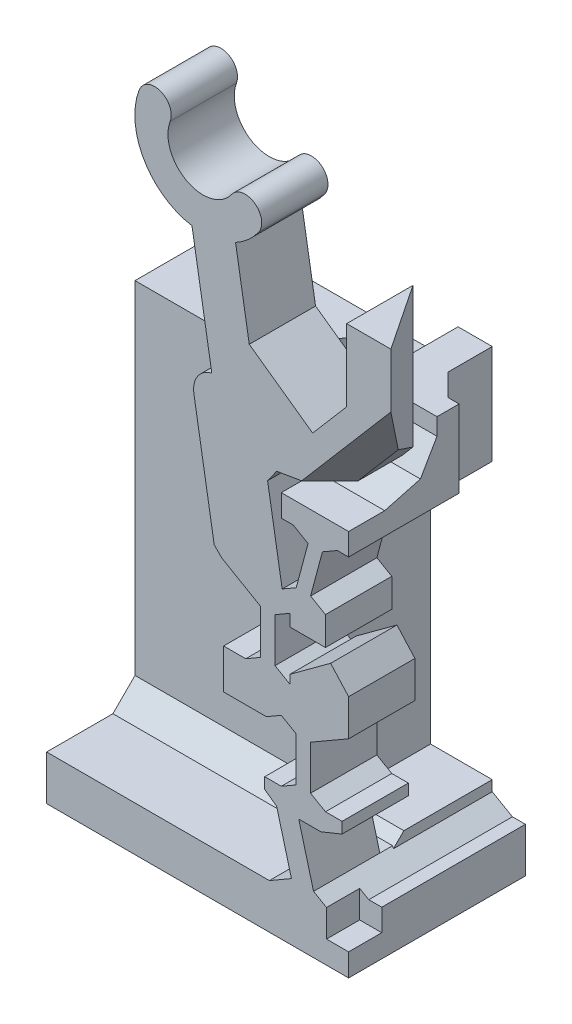
SolidWorks part; units mm, degrees
material "Nylon 6/12"
ref_plane "Front Plane" through (0, 0, 0) normal (0, 0, 1) x (1, 0, 0)
ref_plane "Top Plane" through (0, 0, 0) normal (0, 1, 0) x (1, 0, 0)
ref_plane "Right Plane" through (0, 0, 0) normal (1, 0, 0) x (0, 0, -1)
sketch "Sketch-SkeletonConfigUp" plane through (0, 0, 0) normal (0, 0, 1) x (1, 0, 0)
  line L0 (0, 0) -> (0, -50000) construction
  line L1 (0, 0) -> (4.5811, 6.2164) construction
  line L2 (9.8143, 13.3177) -> (4.5811, 13.945) construction
  line L3 (4.5811, 13.945) -> (2.9713, 10.4094) construction
  line L4 (2.9713, 10.4094) -> (4.5811, 6.2164) construction
  line L5 (4.5811, 13.945) -> (6.2429, 19.1409) construction
  line L6 (2.9713, 10.4094) -> (0.0405, 27.8193) construction
  line L7 (4.5811, 6.2164) -> (9.8143, 13.3177) construction
  line L8 (-587.3593, -797.0242) -> (9.8143, 13.3177) construction
  dimension "D2" = 7.7221
  dimension "D3" = 8.8212
  dimension "D4" = 5.2707
  dimension "D5" = 119.553
  dimension "D6" = 3.8848
  dimension "D7" = 5.4552
  dimension "D8" = 17.6549
  dimension "D9" = 4.4914
  dimension "D10" = 6.745
  dimension "D11" = 145.964
  dimension "D12" = 143.612
sketch "Sketch-SkeletonConfigDown" plane through (0, 0, 0) normal (0, 0, 1) x (1, 0, 0)
  line L0 (0, 0) -> (0, -50000) construction
  line L1 (0, 0) -> (4.5811, 6.2164) construction
  line L2 (9.8143, 13.3177) -> (4.5811, 13.945) construction
  line L3 (4.5811, 13.945) -> (6.1909, 10.4094) construction
  line L4 (6.1909, 10.4094) -> (4.5811, 6.2164) construction
  line L5 (4.5811, 13.945) -> (1.753, 18.6098) construction
  line L6 (6.1909, 10.4094) -> (-8.8652, 19.6294) construction
  line L7 (4.5811, 6.2164) -> (9.8143, 13.3177) construction
  line L8 (-589.9357, -800.5203) -> (9.8143, 13.3177) construction
  dimension "D2" = 7.7221
  dimension "D3" = 8.8212
  dimension "D4" = 5.2707
  dimension "D5" = 119.553
  dimension "D6" = 3.8848
  dimension "D7" = 5.4552
  dimension "D8" = 17.6549
  dimension "D9" = 4.4914
  dimension "D10" = 6.745
  dimension "D11" = 145.964
  dimension "D1" = 143.612
ref_plane "Plane-Cam Base" through (9.128, 0, 0) normal (1, 0, 0) x (0, 0, -1)
ref_plane "Plane-Down-to-Up Derailleur Clearance" through (6.628, 0, 0) normal (1, 0, 0) x (0, 0, -1)
ref_plane "Plane-Cam Cavity Roof" through (5.128, 0, 0) normal (1, 0, 0) x (0, 0, -1)
sketch "Sketch-SwitchBossUp" plane through (0, 0, 0) normal (0, 0, 1) x (1, 0, 0)
  line L0 (3.5811, 11.4759) -> (3.5811, 12.945) construction
  line L2 (6.5405, 21.1774) -> (6.5405, 24.4384)
  line L3 (6.5405, 24.4384) -> (8.5405, 24.4384)
  line L4 (8.5405, 24.4384) -> (8.5405, 20.4384)
  line L5 (5.5811, 12.5552) -> (5.5811, 11.263)
  line L7 (1.5115, 25.1048) -> (2.5464, 18.9575)
  line L8 (-0.4607, 24.7728) -> (0.4359, 19.4465)
  line L9 (2.9713, 10.4094) -> (0.0405, 27.8193) construction
  line L11 (-0.0396, 22.2712) -> (1.9326, 22.6032) construction
  line L15 (6.628, -55) -> (6.628, 55) construction
  line L16 (2.9713, 10.4094) -> (4.5811, 6.2164) construction
  line L17 (3.5811, 12.945) -> (3.5811, 14.945) construction
  line L18 (5.5811, 12.945) -> (5.5811, 14.945) construction
  line L19 (4.2561, 13.945) -> (4.9061, 13.945) construction
  line L20 (3.5811, 14.945) -> (5.5811, 14.945) construction
  line L21 (3.5811, 12.945) -> (5.5811, 12.945) construction
  line L22 (4.5811, 12.945) -> (4.5811, 14.945) construction
  line L23 (4.5811, 6.2164) -> (8.5405, 7.1023) construction
  line L24 (1.9713, 9.4094) -> (1.9713, 11.4094) construction
  line L25 (3.9713, 9.4094) -> (3.9713, 11.4094) construction
  line L26 (3.9713, 9.4094) -> (1.9713, 9.4094) construction
  line L27 (1.9713, 11.4094) -> (3.9713, 11.4094) construction
  line L28 (3.5811, 7.2164) -> (5.5811, 7.2164) construction
  line L29 (3.5811, 7.2164) -> (3.5811, 5.2164) construction
  line L30 (5.5811, 7.2164) -> (5.5811, 5.2164) construction
  line L31 (3.5811, 5.2164) -> (5.5811, 5.2164) construction
  line L32 (4.9061, 6.2164) -> (4.2561, 6.2164) construction
  line L40 (3.2963, 10.4094) -> (2.6463, 10.4094) construction
  line L43 (2.874, 4.5093) -> (0.7934, 4.5093) construction
  line L51 (4.9929, 19.3693) -> (2.5464, 18.9575)
  line L66 (0.0405, 27.8193) -> (0.0405, 50027.8193) construction
  line L74 (0.5455, 12.7717) -> (-0.3728, 18.2264)
  line L75 (0.3841, 13.7302) -> (2.3564, 14.0622) construction
  line L76 (5.5811, 11.263) -> (5.5811, 12.5552) construction
  line L77 (5.5811, 7.6061) -> (6.628, 8.2105)
  line L80 (5.8152, 10.763) -> (6.628, 9.8603)
  line L81 (8.5405, 1033.6218) -> (8.5405, 20.4384) construction
  line L82 (2.5464, 18.9575) -> (3.5585, 12.945) construction
  line L83 (3.6203, 12.5779) -> (2.8784, 16.9852)
  line L84 (2.8784, 16.9852) -> (6.0405, 17.5175)
  line L85 (6.9307, 9.5241) -> (8.5405, 7.7363) construction
  line L88 (3.5811, 16.3347) -> (6.8573, 16.3347)
  line L92 (3.7762, 8.3129) -> (6.9307, 9.5241) construction
  line L93 (6.3311, 4.3267) -> (5.3706, 3.937)
  line L95 (2.5464, 18.9575) -> (2.8784, 16.9852) construction
  line L96 (2.7124, 17.9713) -> (8.5405, 18.9524) construction
  line L97 (2.7124, 17.9713) -> (1.7262, 17.8053) construction
  line L98 (1.9713, 9.0197) -> (0.9713, 9.0197)
  line L99 (0.9713, 9.0197) -> (0.9713, 7.2164)
  line L100 (0.9713, 7.2164) -> (2.9061, 7.2164)
  line L101 (4.5811, 6.2164) -> (6.9307, 9.5241) construction
  line L103 (0.0405, 27.8193) -> (1.9448, 26.4638) construction
  line L104 (6.9307, 9.5241) -> (8.5405, 7.7363) construction
  line L106 (13.4416, 14.945) -> (5.5811, 14.945) construction
  line L107 (1.9713, 9.4094) -> (1.9713, 9.0197) construction
  line L109 (0.0405, 27.8193) -> (-2.1498, 28.6358) construction
  line L110 (8.5405, 20.4384) -> (6.0405, 17.5175)
  line L111 (6.628, 9.8603) -> (6.628, 8.2105)
  line L112 (6.628, 9.8603) -> (6.9307, 9.5241) construction
  line L113 (2.8311, 4.8267) -> (2.8311, 4.3267)
  line L114 (7.3693, 7.7363) -> (7.3563, 7.7363) construction
  line L115 (6.8573, 16.3347) -> (13.4416, 16.3347)
  line L116 (13.4416, 16.3347) -> (13.4416, -1.1653)
  line L117 (13.4416, -1.1653) -> (5.0405, -1.1653)
  line L119 (10.4375, 14.0252) -> (10.4375, 2.1692)
  line L121 (5.0405, -1.1653) -> (5.0405, 1.437) construction
  line L122 (8.237, 12.8031) -> (10.8393, 12.8031) construction
  line L123 (10.8393, 12.8031) -> (13.4416, 12.8031) construction
  line L124 (10.4375, 2.1692) -> (9.128, 0.8597)
  line L125 (8.5405, 7.5847) -> (13.4416, 7.5847) construction
  line L127 (5.5811, 15.3347) -> (5.5811, 14.945) construction
  line L130 (6.0405, 0.8597) -> (9.128, 0.8597)
  line L132 (2.8311, 4.3267) -> (3.3706, 3.937)
  line L133 (2.9713, 10.4094) -> (6.1909, 10.4094) construction
  line L134 (4.5811, 10.4094) -> (4.5811, 13.945) construction
  line L135 (4.5811, 10.4094) -> (4.5811, 6.2164) construction
  line L136 (0.8973, 12.4192) -> (0.5455, 12.7717)
  line L137 (3.9713, 9.4094) -> (5.5811, 7.2164) construction
  line L139 (5.8152, 10.763) -> (3.9713, 9.4094)
  line L141 (4.0405, 1.437) -> (3.0405, 0.8597)
  line L142 (3.0405, 0.8597) -> (3.0405, -1.1653)
  line L143 (8.5405, 20.4384) -> (8.5405, 18.9524) construction
  line L145 (8.5405, 17.9384) -> (8.5405, -49992.0368) construction
  line L147 (5.5811, 11.263) -> (5.5811, 12.5552) construction
  line L149 (6.3311, 4.8267) -> (6.3311, 4.3267)
  line L150 (3.0405, -1.1653) -> (5.0405, -1.1653)
  line L151 (3.3706, 3.937) -> (5.3706, 3.937) construction
  line L152 (4.792, 14.945) -> (4.2561, 12.945)
  line L153 (5.442, 14.945) -> (4.9061, 12.945)
  line L157 (3.5811, 16.3347) -> (3.5811, 15.3347)
  line L158 (6.117, 15.3347) -> (9.128, 15.3347)
  line L162 (3.2963, 11.4094) -> (3.2963, 9.4094)
  line L164 (2.6463, 11.4094) -> (2.6463, 9.4094)
  line L169 (4.2561, 7.2164) -> (4.2561, 5.2164)
  line L170 (4.9061, 5.2164) -> (4.9061, 7.2164)
  line L175 (4.2561, 7.2164) -> (3.5811, 7.6061)
  line L176 (4.9061, 7.2164) -> (5.5811, 7.6061)
  line L177 (5.5811, 7.2164) -> (5.5811, 7.6061) construction
  line L179 (4.2561, 5.2164) -> (3.5811, 4.8267)
  line L180 (3.5811, 5.2164) -> (3.5811, 4.8267) construction
  line L181 (3.5811, 4.8267) -> (2.8311, 4.8267)
  line L183 (4.9061, 5.2164) -> (5.5811, 4.8267)
  line L184 (5.5811, 5.2164) -> (5.5811, 4.8267) construction
  line L186 (9.128, -55) -> (9.128, 55) construction
  line L187 (2.6463, 9.4094) -> (1.9713, 9.0197)
  line L188 (3.2963, 9.4094) -> (3.9713, 9.0197)
  line L189 (3.2963, 11.4094) -> (3.9713, 11.7991)
  line L190 (2.6463, 11.4094) -> (0.8973, 12.4192)
  line L191 (3.9713, 11.4094) -> (3.9713, 11.7991) construction
  line L192 (3.9713, 11.7991) -> (3.9713, 11.263)
  line L193 (4.9061, 12.945) -> (5.5811, 12.5552)
  line L194 (4.2561, 12.945) -> (3.6203, 12.5779)
  line L195 (3.9713, 11.263) -> (5.5811, 11.263)
  line L196 (3.9713, 9.4094) -> (3.9713, 9.0197)
  line L197 (3.5811, 7.2164) -> (3.5811, 7.6061) construction
  line L199 (3.5811, 7.6061) -> (2.9061, 7.2164)
  line L200 (5.5811, 4.8267) -> (6.3311, 4.8267)
  line L201 (2.8311, 4.3267) -> (2.8311, 3.937) construction
  line L202 (2.8311, 3.937) -> (3.3706, 3.937) construction
  line L203 (10.4375, 14.0252) -> (9.128, 15.3347)
  line L204 (5.0405, 1.437) -> (3.0405, 1.437) construction
  line L205 (3.0405, 1.437) -> (3.0405, 0.8597) construction
  line L206 (5.0405, 1.437) -> (6.0405, 0.8597)
  line L207 (8.5405, 18.9524) -> (8.5405, 17.9384) construction
  line L208 (6.0405, 17.5175) -> (8.5405, 17.9384) construction
  line L209 (8.5405, 20.4384) -> (8.5405, 17.9384) construction
  line L210 (6.5405, 21.1774) -> (4.9929, 19.3693)
  line L211 (5.0405, 1.437) -> (4.3706, 3.937)
  line L212 (4.0405, 1.437) -> (3.3706, 3.937)
  line L213 (5.3706, 3.937) -> (4.3706, 3.937)
  line L214 (4.792, 14.945) -> (4.1169, 15.3347)
  line L215 (4.1169, 15.3347) -> (3.5811, 15.3347)
  line L216 (5.442, 14.945) -> (6.117, 15.3347)
  line L217 (5.5811, 12.945) -> (5.5811, 12.5552) construction
  line L218 (5.442, 14.945) -> (5.442, 15.3347) construction
  line L219 (6.117, 15.3347) -> (4.1169, 15.3347) construction
  arc A0 (1.5115, 25.1048) -> (2.5558, 26.0289) centre (0.0405, 27.8193) ccw
  arc A1 (-0.4607, 24.7728) -> (-2.8525, 28.8978) centre (0.0405, 27.8193) cw
  arc A2 (-2.8525, 28.8978) -> (-1.447, 28.3738) centre (-2.1498, 28.6358) cw
  arc A3 (2.5558, 26.0289) -> (1.3338, 26.8987) centre (1.9448, 26.4638) ccw
  arc A4 (-1.447, 28.3738) -> (1.3338, 26.8987) centre (0.0405, 27.8193) ccw
  arc A5 (3.5811, 12.945) -> (3.5811, 14.945) centre (3.1778, 13.945) ccw construction
  arc A6 (5.5811, 12.945) -> (5.5811, 14.945) centre (5.9843, 13.945) cw construction
  arc A7 (2.5293, 9.921) -> (1.9713, 11.4094) centre (1.568, 10.4094) ccw construction
  arc A8 (3.9713, 11.4094) -> (3.9713, 9.4094) centre (4.3745, 10.4094) ccw construction
  arc A9 (3.5811, 7.2164) -> (3.5811, 5.2164) centre (3.1779, 6.2164) cw construction
  arc A10 (5.5811, 7.2164) -> (5.5811, 5.2164) centre (5.9844, 6.2164) ccw construction
  arc A19 (-0.3728, 18.2264) -> (0.4359, 19.4465) centre (0.6836, 18.4042) cw
  circle A28 centre (0.0405, 27.8193) radius 2.3375 construction
  arc A29 (1.9713, 9.4094) -> (2.5293, 9.921) centre (1.568, 10.4094) ccw construction
  point P53 (4.5811, 13.945)
  point P63 (2.9713, 10.4094)
  point P93 (0.9465, 22.4372)
  dimension "D23" = 1.5875
  dimension "D24" = 0.75
  dimension "D2" = 2
  dimension "D5" = 2
  dimension "D6" = 0.65
  dimension "D8" = 42
  dimension "D7" = 2
  dimension "D11" = 8.5
  dimension "D14" = 7.5
  dimension "D4" = 3
  dimension "D16" = 42
  dimension "D27" = 120
  dimension "D28" = 120
  dimension "D29" = 120
  dimension "D30" = 120
  dimension "D31" = 120
  dimension "D32" = 120
  dimension "D33" = 120
  dimension "D34" = 120
  dimension "D17" = 0.5
  dimension "D20" = 3.5
  dimension "D21" = 1
  dimension "D18" = 45
  dimension "D9" = 17.5
  dimension "D22" = 1
  dimension "D15" = 45
  dimension "D38" = 2
  dimension "D39" = 0.5
  dimension "D40" = 60
  dimension "D41" = 1
  dimension "D42" = 45
  dimension "D43" = 120
  dimension "D44" = 2
  dimension "D45" = 2.5
  dimension "D46" = 2.5
  dimension "D47" = 4
  dimension "D48" = 2
  dimension "D10" = 15
  dimension "D12" = 2.5
  dimension "D13" = 1
  dimension "D19" = 1
  dimension "D25" = 15
  dimension "D26" = 120
  dimension "D35" = 120
extrude "Boss-Switch Body" add sketch "Sketch-SwitchBossUp" along normal blind 3
sketch "Sketch1" plane through (0, 0, 0) normal (0, 0, -1) x (-1, 0, 0)
  line L1 (-7.5811, -1.1653) -> (0.4122, -1.1653)
  line L2 (-7.5811, -1.1653) -> (-7.5811, 0.8597)
  line L4 (0.4122, -1.1653) -> (0.4122, 0.8597)
  line L5 (-3.5811, 18.8347) -> (-7.5811, 18.8347)
  line L10 (-7.5811, 18.8347) -> (-7.5811, 15.3347)
  line L11 (-4.0405, 1.437) -> (-5.0405, 1.437)
  line L12 (-7.5811, 15.3347) -> (-3.5811, 15.3347)
  line L13 (-4.0405, 1.437) -> (-3.0405, 0.8597)
  line L14 (-3.5811, 15.3347) -> (-3.5811, 18.8347)
  line L20 (-4.3706, 3.937) -> (-5.0405, 1.437) construction
  line L22 (-3.0405, -1.1653) -> (-13.4416, -1.1653) construction
  line L23 (-3.0405, 0.8597) -> (0.4122, 0.8597)
  line L24 (-5.0405, 1.437) -> (-6.0405, 0.8597)
  line L25 (-6.0405, 0.8597) -> (-7.5811, 0.8597)
  line L27 (-3.5811, 16.3347) -> (-3.5811, 15.3347) construction
  dimension "D1" = 3.5
  dimension "D4" = 4
extrude "Boss-Flange Width" add sketch "Sketch1" along normal blind 5
ref_plane "Plane-Sta2Sit Groove" through (0.0405, 0, 0) normal (1, 0, 0) x (0, 0, -1)
ref_plane "Plane-Cam Outer Surface" through (-12.0395, 0, 0) normal (1, 0, 0) x (0, 0, -1)
ref_plane "Plane-FlangeTop" through (-7.0395, 0, 0) normal (1, 0, 0) x (0, 0, -1)
sketch "Sketch2" plane through (-7.0395, 0, 0) normal (1, 0, 0) x (0, 0, -1)
  line L0 (5, 15.3347) -> (-3, 15.3347) construction
  line L1 (5, 17.3347) -> (1, 17.3347)
  line L2 (5, 17.3347) -> (5, 15.3347)
  line L3 (5, 15.3347) -> (1, 15.3347)
  line L4 (1, 17.3347) -> (1, 15.3347)
  line L10 (-3, -1.1653) -> (-3, 16.3347) construction
  line L11 (5, 0.8597) -> (-3, 0.8597)
  line L12 (5, 0.8597) -> (5, -1.1653)
  line L13 (5, -1.1653) -> (-3, -1.1653)
  line L14 (-3, 0.8597) -> (-3, -1.1653)
  line L15 (0, 10.4094) -> (0, 27.8193) construction
  line L17 (5, 0.8597) -> (5, -1.1653) construction
  line L18 (-3, 0.8597) -> (0, 0.8597) construction
  dimension "D1" = 1
  dimension "D2" = 2
extrude "Boss-Flange Height" add sketch "Sketch2" along normal up to surface (11.6675 mm away)
sketch "Sketch10" plane through (0, 15.3347, 0) normal (0, 1, 0) x (1, 0, 0)
  line L0 (9.128, -55) -> (9.128, 55) construction
  line L1 (7.5811, 5) -> (5.128, 5)
  line L2 (7.5811, 5) -> (7.5811, 2)
  line L3 (7.5811, 2) -> (5.128, 2)
  line L5 (4.628, 7) -> (4.628, 1) construction
  line L6 (3.5811, 1) -> (-7.0395, 1) construction
  line L8 (5.128, 5) -> (5.128, 2)
  dimension "D1" = 1
  dimension "D2" = 0.5
  dimension "D3" = 4.5
extrude "Cut-Up-To-Down Derailleur Clearance" cut sketch "Sketch10" along normal up to next
sketch "Sketch17" plane through (0, 15.3347, 0) normal (0, -1, 0) x (1, 0, 0)
  line L0 (5.128, -5) -> (-7.0395, -5)
  line L1 (5.128, -5) -> (-7.0395, -5) construction
  line L2 (-7.0395, -5) -> (-7.0395, -1)
  line L3 (-7.0395, -1) -> (5.128, -1)
  line L4 (5.128, -1) -> (5.128, -5)
  line L5 (-7.0395, -1) -> (-7.0395, -5) construction
extrude "Boss-Flange Support" add sketch "Sketch17" along normal up to surface (14.475 mm away) up to face at (-1.9995, 0.8597, -1)
sketch "Sketch-HolePositions" plane through (0, -1.1653, 0) normal (0, -1, 0) x (1, 0, 0)
  line L0 (-7.0395, -3) -> (7.5811, -3) construction
  line L1 (7.5811, -5) -> (-7.0395, -5) construction
  line L2 (7.5811, -5) -> (7.5811, 0) construction
  line L4 (-7.0395, -22.2167) -> (-7.0395, 22.2167) construction
  line L5 (3.5811, -1) -> (3.5811, -5) construction
  point P6 (-4.0395, -3)
  point P7 (0.5811, -3)
  dimension "D1" = 3
  dimension "D2" = 3
  dimension "D3" = 2
sketch "Sketch6" plane through (0, -1.1653, 0) normal (0, -1, 0) x (-1, 0, 0)
  point P0 (4.0395, 3)
  point P3 (-0.5811, 3)
hole_wizard "Tap Drill for M2x0.4 Tap1" positions "Sketch6" profile "Sketch5" hole size "M2x0.4" standard "ANSI Metric" end condition through all
sketch "Sketch5" plane through (-4.0395, -1.1653, -3) normal (1, 0, 0) x (0, 0, -1)
  line L0 (0, 0) -> (0, 30.5511)
  line L1 (0, 30.5511) -> (0.8, 30.5511)
  line L2 (0.8, 30.5511) -> (0.8, 0)
  line L5 (0.8, 0) -> (0, 0)
  line L11 (0, -6.35) -> (0, 107.95) construction
  dimension "Thru Hole Dia." = 1.6
  dimension "Thru Hole Depth" = 30.5511
sketch "Sketch9" plane through (0, -1.1653, 0) normal (0, -1, 0) x (1, 0, 0)
  point P0 (-4.0395, -3)
  point P3 (0.5811, -3)
hole_wizard "M2 Clearance Hole2" positions "Sketch9" profile "Sketch8" hole size "M2" standard "ANSI Metric"
sketch "Sketch8" plane through (-4.0395, -1.1653, -3) normal (1, 0, 0) x (0, 0, -1)
  line L0 (0, 0) -> (0, 15.721)
  line L1 (0, 15.721) -> (1.2, 15)
  line L2 (1.2, 15) -> (1.2, 0)
  line L5 (1.2, 0) -> (0, 0)
  line L10 (0, 15.721) -> (-1.2, 15) construction
  line L11 (0, -6.35) -> (0, 107.95) construction
  dimension "Hole Dia." = 2.4
  dimension "Hole Depth" = 15
  dimension "Drill Angle" = 118
sketch "Sketch-Measurements for Derailleur Ramps" plane through (0, 0, 0) normal (0, 0, 1) x (1, 0, 0)
  line L0 (2.8784, 16.9852) -> (2.5464, 18.9575)
  line L1 (2.7124, 17.9713) -> (1.7262, 17.8053)
  line L2 (2.9713, 10.4094) -> (0.0405, 27.8193) construction
  line L3 (1.7262, 17.8053) -> (-1.8937, 15.3603)
  line L4 (6.1909, 10.4094) -> (-8.8652, 19.6294) construction
  line L5 (1.7262, 17.8053) -> (2.6012, 12.6077)
  line L6 (2.6012, 12.6077) -> (-1.8937, 15.3603)
  line L7 (-0.0837, 16.5828) -> (-0.0837, 17.8053)
  line L8 (-0.0837, 17.8053) -> (1.7262, 17.8053)
  line L9 (6.1909, 10.4094) -> (2.9713, 10.4094)
  line L10 (5.386, 8.3129) -> (3.7762, 8.3129)
  line L12 (6.1909, 10.4094) -> (4.5811, 6.2164) construction
  line L13 (4.5811, 8.3129) -> (4.5811, 8.7912)
  line L14 (4.5811, 6.2164) -> (5.386, 8.3129)
  line L15 (2.9713, 10.4094) -> (4.5811, 6.2164) construction
  line L16 (3.7762, 8.3129) -> (4.5811, 6.2164)
  line L17 (5.386, 8.3129) -> (5.386, 8.7912)
  dimension "D1" = 1.81
  dimension "D2" = 0.8049
sketch "Sketch12" plane through (0, 24.4384, 0) normal (0, 1, 0) x (1, 0, 0)
  line L0 (6.5405, 0) -> (8.5405, -3)
  line L1 (8.5405, -3) -> (8.5405, 0)
  line L2 (8.5405, 0) -> (6.5405, 0)
extrude "Cut-Up-to-Down Cantilever Slope" cut sketch "Sketch12" against normal up to next
ref_plane "Plane1" through (0, 7.1023, 0) normal (0, 1, 0) x (1, 0, 0)
sketch "Sketch-Derailleur Location" plane through (0, 7.1023, 0) normal (0, 1, 0) x (1, 0, 0)
  line L0 (8.5405, 0) -> (8.5405, -3)
  line L1 (4.0405, -3) -> (3.0405, -3) construction
  line L2 (-119237.4187, 0) -> (9.8143, 0) construction
  point P0 (8.5405, 0)
  point P8 (8.5405, -1.5)
ref_plane "Plane-Cantilever Cut" [suppressed] through (7.0848, 8.5204, -1.9058) normal (-0.6301, -0.7578, 0.1695) x (-0.7765, 0.6151, -0.1368)
sketch "Sketch14" [suppressed] plane through (7.0848, 8.5204, -1.9058) normal (-0.6301, -0.7578, 0.1695) x (-0.7765, 0.6151, -0.1368)
  line L0 (2.3023, -1.6911) -> (-0.3551, -1.6911)
  line L2 (2.3023, -4.3362) -> (2.3023, -1.6911)
  line L3 (-0.3551, -1.6911) -> (-0.3551, -4.4608)
  line L5 (-0.3551, -4.4608) -> (1.0087, -5.0843)
  line L6 (1.0087, -5.0843) -> (2.3023, -4.3362)
extrude "Cut-Down-to-Up Cantilever Slope" [suppressed] cut sketch "Sketch14" against normal up to next
sketch "Sketch16" plane through (0, 0, 0) normal (0, 0, -1) x (-1, 0, 0)
  line L0 (-7.5811, 18.8347) -> (-13.4416, 18.8347)
  line L1 (-13.4416, 18.8347) -> (-13.4416, -1.1653)
  line L2 (-13.4416, -1.1653) -> (-6.628, -1.1653)
  line L3 (-13.4416, -1.1653) -> (-5.0405, -1.1653) construction
  line L4 (-6.628, -1.1653) -> (-6.628, 5.2038)
  line L5 (-6.628, 5.2038) -> (-8.0037, 5.2038)
  line L6 (-8.0037, 5.2038) -> (-8.0037, 12.0484)
  line L7 (-8.0037, 12.0484) -> (-6.628, 12.0484)
  line L8 (-6.628, 12.0484) -> (-6.628, 17.9477)
  line L9 (-6.628, 55) -> (-6.628, -55) construction
  line L10 (-3.5811, 18.8347) -> (-6.5405, 18.8347) construction
  line L11 (-7.5811, 18.8347) -> (-6.628, 17.9477)
extrude "Cut-Down-to-Up Derailleur Clearance" cut sketch "Sketch16" against normal through all and the other way through all
ref_plane "Plane-Symmetry Plane" through (0, 0, 1.5) normal (0, 0, 1) x (1, 0, 0)
sketch "Sketch-Cable Center Point" plane through (0, 0, 1.5) normal (0, 0, 1) x (1, 0, 0)
  line L0 (0.0405, 27.8193) -> (0.1722, 27.0366)
  line L1 (2.9713, 10.4094) -> (0.0405, 27.8193) construction
  point P0 (0.0405, 27.8193)
  dimension "D1" = 0.7937
chamfer "Chamfer-Flange Support" distance 1.5 angle 45 1 edges at (3.5811, 17.3347, -3)
chamfer "Chamfer-Flange Support 2" distance 1 angle 45 2 edges at (5.128, 17.0847, -2) (5.128, 15.3347, -1.5)
chamfer "Chamfer-Flange Support 3" distance 1 angle 45 1 edges at (-1.9995, 0.8597, -1)
sketch "Sketch18" plane through (6.628, 0, 0) normal (1, 0, 0) x (0, 0, -1)
  line L1 (-3, -0.1403) -> (-1.5, -0.1403)
  line L2 (-3, -0.1403) -> (-3, 1.437)
  line L3 (-3, 1.437) -> (-1.5, 1.437)
  line L4 (-1.5, -0.1403) -> (-1.5, 1.437)
  line L5 (0.5774, 1.437) -> (0, 1.437) construction
  line L6 (-3, -1.1653) -> (-3, 0.8597) construction
  line L7 (-3, 0.8597) -> (5, 0.8597) construction
  dimension "D1" = 1.5
  dimension "D2" = 1
extrude "Cut-Down-to-Up Derailleur Clearance 2" cut sketch "Sketch18" against normal blind 1
sketch "Sketch19" plane through (0, 0, 0) normal (0, 0, 1) x (1, 0, 0)
  line L7 (3.5811, 18.8983) -> (6.628, 18.8983)
  line L8 (6.628, 18.8983) -> (6.628, 16.3347)
  line L9 (6.628, 16.3347) -> (3.5811, 16.3347)
  line L10 (3.5811, 16.3347) -> (3.5811, 18.8983)
  line L11 (6.628, 16.3347) -> (6.628, 17.9477) construction
extrude "Cut-Up-to-Down Cantilever Clearance" cut sketch "Sketch19" against normal up to surface (1 mm away) up to face at (1.4435, 12.7784, -1)
chamfer "Chamfer1" distance 1 angle 60 1 edges at (5.1045, 16.3347, -1) first distance on face at (5.1045, 16.3347, 1)
chamfer "Chamfer3" distance 0.75 angle 60 1 edges at (3.5811, 16.7007, -1) first distance on face at (3.5811, 16.2811, 0.8)
chamfer "Chamfer4" distance 0.5 angle 60 1 edges at (4.205, 15.3347, -1) first distance on face at (5.0385, 15.3347, 0.5227)
chamfer "Chamfer5" distance 0.5 angle 45 1 edges at (2.8784, 16.9852, 1.5)
chamfer "Chamfer6" distance 2.5 angle 45 1 edges at (2.5464, 18.9575, 1.5)
chamfer "Chamfer7" distance 1 angle 45 1 edges at (7.2905, 18.978, 3)
sketch "Sketch22" plane through (0, 0, 0) normal (0, 0, 1) x (1, 0, 0)
  line L0 (6.628, 17.9477) -> (7.5811, 18.8347) construction
  line L1 (6.628, 18.8347) -> (7.5811, 18.8347) construction
  line L2 (6.628, 17.9477) -> (6.628, 18.8347) construction
  line L3 (6.628, 17.9477) -> (7.5811, 18.8347)
  line L4 (6.628, 18.8347) -> (7.5811, 18.8347)
  line L5 (6.628, 17.9477) -> (6.628, 18.8347)
extrude "Cut-Extrude3" cut sketch "Sketch22" against normal up to next
chamfer "Chamfer8" distance 0.5 angle 45 1 edges at (5.1045, 16.3347, 0) first distance on face at (4.2965, 17.2286, -0.5161)
sketch "Sketch23" plane through (0, 0, -1) normal (0, 0, 1) x (1, 0, 0)
  line L0 (5.128, 1.8597) -> (2.3369, 1.8597)
  line L1 (-7.0395, 1.8597) -> (5.128, 1.8597) construction
  line L2 (2.3369, 1.8597) -> (2.3369, 14.3347)
  line L3 (2.3369, 14.3347) -> (5.128, 14.3347)
  line L4 (5.128, 14.3347) -> (5.128, 1.8597)
extrude "Cut-Extrude4" cut sketch "Sketch23" against normal through all
equation "\"axle-diameter\"=2"
equation "\"switch-thickness\"=12"
equation "\"base-width\"=4.0"
equation "\"axle-bushing-radius\"=3"
equation "\"clearance\"= 0.25"
equation "\"arm-width\"=1.5"
equation "\"min-diameter\"=70"
equation "\"alpha\"=143.6120"
equation "\"gamma\"=119.5526"
equation "\"delta\"=145.9637"
equation "\"epsilon\"=6.7452"
equation "\"l_AB\"=8.8212"
equation "\"l_AC\"=4.4914"
equation "\"l_BD\"=5.2707"
equation "\"l_CD\"=3.8848"
equation "\"l_CE\"=17.6549"
equation "\"l_DF\"=5.4552"
equation "\"l_OA\"=7.7221"
equation "\"D2@Sketch-SkeletonConfigUp\" = \"l_OA\""
equation "\"D3@Sketch-SkeletonConfigUp\" = \"l_AB\""
equation "\"D4@Sketch-SkeletonConfigUp\" = \"l_BD\""
equation "\"D5@Sketch-SkeletonConfigUp\" = \"gamma\""
equation "\"D6@Sketch-SkeletonConfigUp\" = \"l_CD\""
equation "\"D7@Sketch-SkeletonConfigUp\" = \"l_DF\""
equation "\"D8@Sketch-SkeletonConfigUp\" = \"l_CE\""
equation "\"D9@Sketch-SkeletonConfigUp\" = \"l_AC\""
equation "\"D_groove\"=3.175"
equation "\"D7@Sketch-SkeletonConfigDown\" = \"l_DF\""
equation "\"D6@Sketch-SkeletonConfigDown\" = \"l_CD\""
equation "\"D2@Sketch-SkeletonConfigDown\" = \"l_OA\""
equation "\"D3@Sketch-SkeletonConfigDown\" = \"l_AB\""
equation "\"D9@Sketch-SkeletonConfigDown\" = \"l_AC\""
equation "\"D8@Sketch-SkeletonConfigDown\" = \"l_CE\""
equation "\"D5@Sketch-SkeletonConfigDown\" = \"gamma\""
equation "\"D4@Sketch-SkeletonConfigDown\" = \"l_BD\""
equation "\"D1@Sketch-SkeletonConfigDown\" = \"alpha\""
equation "\"hinge_length\"=1.5"
equation "\"hinge_depth\"=0.25"
equation "\"D10@Sketch-SkeletonConfigUp\"=\"epsilon\""
equation "\"D11@Sketch-SkeletonConfigUp\"=\"delta\""
equation "\"D12@Sketch-SkeletonConfigUp\"=\"alpha\""
equation "\"D11@Sketch-SkeletonConfigDown\"=\"delta\""
equation "\"D10@Sketch-SkeletonConfigDown\"=\"epsilon\""
equation "\"EE_dx\"=8.9056"
equation "\"EE_dy\"=8.1898"
equation "\"r_groove\"=\"D_groove\"/2"
equation "\"t_wall\"=25.4/16"
equation "\"width_lower\"=\"D_groove\"+\"t_wall\""
equation "\"cable_to_bottom\"=30.6257"
equation "\"switch_EE-up_base_dy\"=24"
equation "\"switch_EE-down_base_dy\"=16"
equation "\"D_axle\"=25.4/8"
equation "\"D_up_to_down\"=16"
equation "\"D_down_to_up\"=25"
equation "\"t_cam_base\"=7.5"
equation "\"D23@Sketch-SwitchBossUp\"=\"D_groove\"/2"
equation "\"D1@Sketch-Cable Center Point\"=\"D_groove\"/4"
